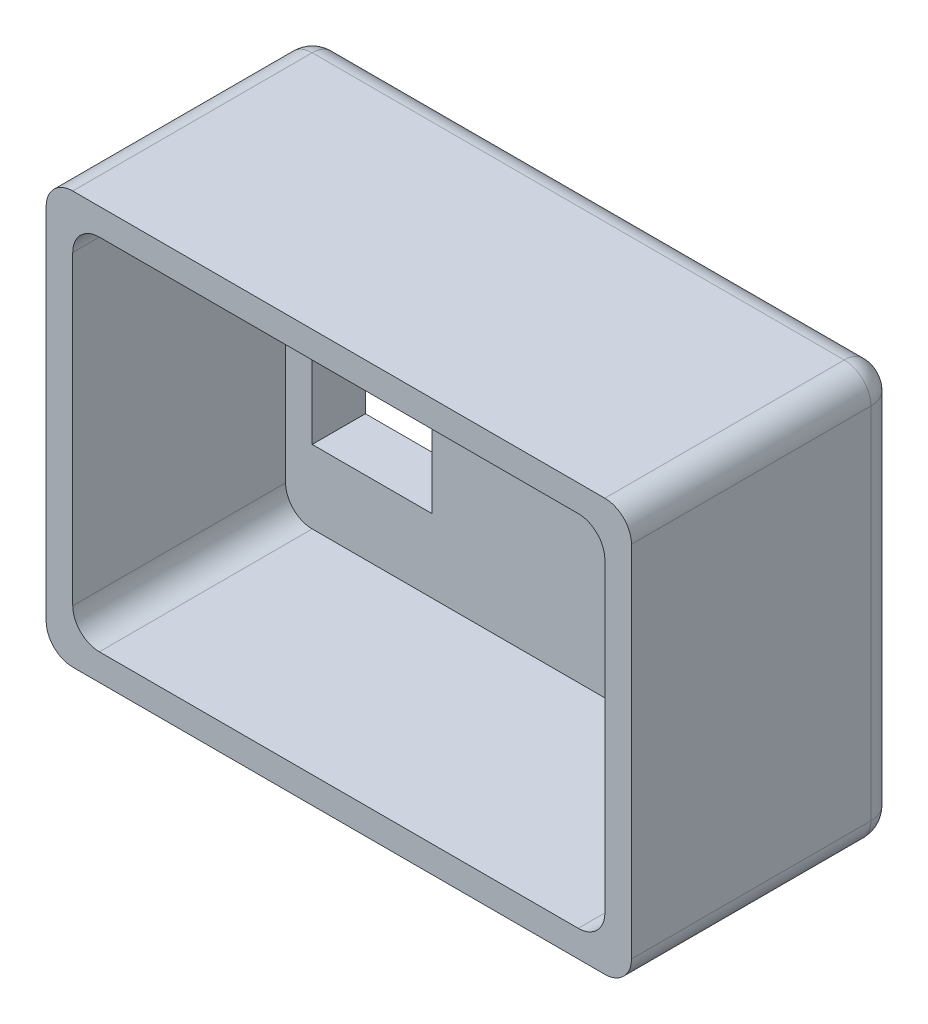
SolidWorks part; units mm, degrees
ref_plane "Plan de face" through (0, 0, 0) normal (0, 0, 1) x (1, 0, 0)
ref_plane "Plan de dessus" through (0, 0, 0) normal (0, 1, 0) x (1, 0, 0)
ref_plane "Plan de droite" through (0, 0, 0) normal (1, 0, 0) x (0, 0, -1)
sketch "Esquisse1" plane through (0, 0, 0) normal (0, 0, 1) x (1, 0, 0)
  line L1 (0, 0) -> (20, 0)
  line L2 (0, 0) -> (0, 13.5)
  line L3 (0, 13.5) -> (20, 13.5)
  line L4 (20, 0) -> (20, 13.5)
  dimension "D1" = 20
  dimension "D2" = 13.5
extrude "Boss.-Extru.1" add sketch "Esquisse1" along normal blind 2
extrude "Extru.-Mince1" add sketch "Esquisse1<2>" along normal blind 10 thin thin type one direction wall 1
sketch "Esquisse1<2>" plane through (0, 0, 0) normal (0, 0, 1) x (1, 0, 0) same geometry as "Esquisse1"
sketch "Esquisse2" plane through (0, 0, 2) normal (0, 0, 1) x (1, 0, 0)
  line L1 (1, 11.75) -> (5.5, 11.75)
  line L2 (1, 11.75) -> (1, 2.75)
  line L3 (1, 2.75) -> (5.5, 2.75)
  line L4 (5.5, 11.75) -> (5.5, 2.75)
  line L6 (0, 13.5) -> (0, 0) construction
  line L8 (-1, -1) -> (21, -1) construction
  dimension "D1" = 4.5
  dimension "D2" = 9
  dimension "D3" = 3.75
  dimension "D4" = 1
extrude "Enlèv. mat.-Extru.1" cut sketch "Esquisse2" against normal blind 10
fillet "Congé1" radius 1 8 edges at (0, 0, 6) (0, 13.5, 6) (20, 13.5, 6) (20, 0, 6) (-1, -1, 5) (-1, 14.5, 5) (21, -1, 5) (21, 14.5, 5)
fillet "Congé2" radius 1 8 edges at (-0.7071, -0.7071, 0) (-1, 6.75, 0) (-0.7071, 14.2071, 0) (10, 14.5, 0) (20.7071, 14.2071, 0) (21, 6.75, 0) (20.7071, -0.7071, 0) (10, -1, 0)
